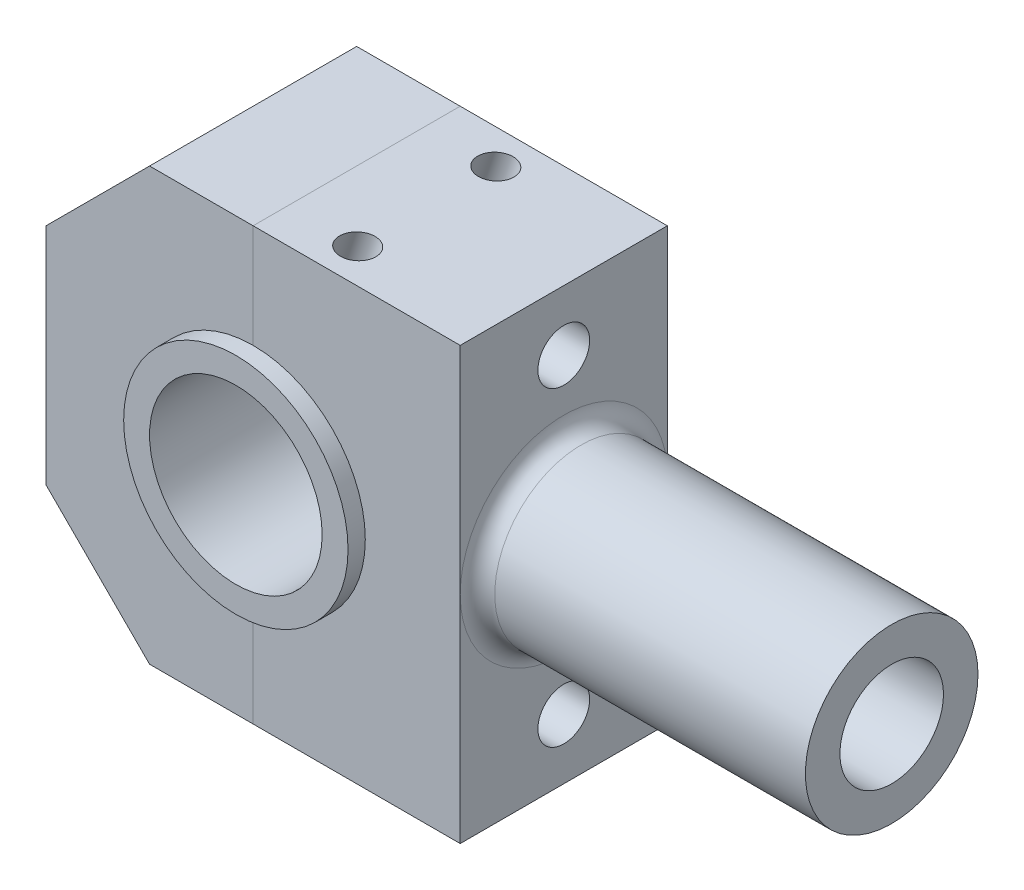
SolidWorks part; units mm, degrees
ref_plane "Front Plane" through (0, 0, 0) normal (0, 0, 1) x (1, 0, 0)
ref_plane "Top Plane" through (0, 0, 0) normal (0, 1, 0) x (1, 0, 0)
ref_plane "Right Plane" through (0, 0, 0) normal (1, 0, 0) x (0, 0, -1)
sketch "Sketch1" plane through (0, 0, 0) normal (0, 0, 1) x (1, 0, 0)
  line L0 (0, 0) -> (0, -15353.2497) construction
  line L1 (0, 0) -> (-15353.2497, 0) construction
  line L2 (0, 12.5) -> (0, 5)
  line L3 (-6, 12.5) -> (12, 12.5)
  line L4 (-12, 6.5) -> (-12, -6.5)
  line L5 (-6, -12.5) -> (12, -12.5)
  line L6 (12, 12.5) -> (12, -12.5)
  line L9 (0, -12.5) -> (0, -5)
  line L10 (0, 6.5) -> (-12, 6.5) construction
  line L11 (0, -6.5) -> (-12, -6.5) construction
  line L12 (-12, 6.5) -> (-6, 12.5)
  line L13 (-12, -6.5) -> (-6, -12.5)
  circle A0 centre (0, 0) radius 6.5
  circle A1 centre (0, 0) radius 5
  point P26 (12, 0)
  dimension "D1" = 13
  dimension "D2" = 10
  dimension "D3" = 25
  dimension "D4" = 12
  dimension "D5" = 6
  dimension "D6" = 6
extrude "Boss-Extrude1" add sketch "Sketch1" along normal mid plane 12 contours A0 L9 L5 L6 L3 L2 region at (6.9207, 0, 0)
extrude "Boss-Extrude2" add sketch "Sketch1<3>" along normal mid plane 12 separate body contours A0 L2 L3 L12 L4 L13 L5 L9 region at (-0.2773, 9.5, 0)
sketch "Sketch1<3>" plane through (0, 0, 0) normal (0, 0, 1) x (1, 0, 0) same geometry as "Sketch1"
sketch "Sketch2" plane through (12, 0, 0) normal (1, 0, 0) x (0, 0, -1)
  line L0 (0, 0) -> (0, 50000) construction
  line L1 (0, 0) -> (50000, 0) construction
  circle A0 centre (0, 0) radius 5
  circle A1 centre (0, 9) radius 1.5
  circle A2 centre (0, 0) radius 3
  circle A3 centre (0, -9) radius 1.5
  dimension "D1" = 10
  dimension "D2" = 6
  dimension "D3" = 3
  dimension "D4" = 9
extrude "Boss-Extrude3" add sketch "Sketch2" along normal blind 19 contours A0 A2 region at (12, 0, 4.8586)
cosmetic thread "Cosmetic Thread1" parameters "D2"=8
extrude "Cut-Extrude1" cut sketch "Sketch2<3>" against normal blind 18 contours A1 | A3 region at (12, 9, 0) region at (12, -9, 0)
sketch "Sketch2<3>" plane through (12, 0, 0) normal (1, 0, 0) x (0, 0, -1) same geometry as "Sketch2"
cosmetic thread "Cosmetic Thread2" parameters "D2"=4
cosmetic thread "Cosmetic Thread3" parameters "D2"=4
extrude "Boss-Extrude4" add sketch "Sketch1<4>" along normal mid plane 14 separate body contours A1 L9 A0 L2 | A1 L2 A0 L9 region at (4.4934, 4.4934, 0) region at (-0.1453, 5.75, 0)
sketch "Sketch1<4>" plane through (0, 0, 0) normal (0, 0, 1) x (1, 0, 0) same geometry as "Sketch1"
ref_plane "Plane1" through (4.8196, 14.8331, 0) normal (0.309, 0.9511, 0) x (0, 0, -1)
sketch "Sketch3" plane through (4.8196, 14.8331, 0) normal (0.309, 0.9511, 0) x (0, 0, -1)
  line L0 (0, 0) -> (-50000, 0) construction
  line L1 (0, 0) -> (0, -50000) construction
  circle A0 centre (-4, 0) radius 1
  circle A1 centre (4, 0) radius 1
  dimension "D1" = 2
  dimension "4" = 4
extrude "Cut-Extrude2" cut sketch "Sketch3" against normal up to surface (10.6974 mm away) up to face at (5, 0, 7)
fillet "Fillet1" radius 1 1 edges at (12, 0, -5)
